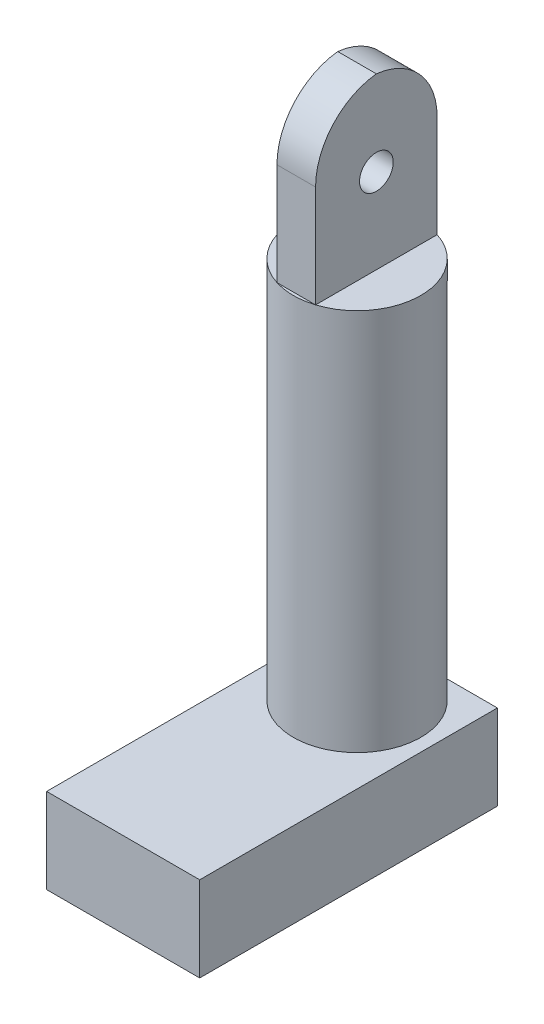
SolidWorks part; units mm, degrees
ref_plane "Front Plane" through (0, 0, 0) normal (0, 0, 1) x (1, 0, 0)
ref_plane "Top Plane" through (0, 0, 0) normal (0, 1, 0) x (1, 0, 0)
ref_plane "Right Plane" through (0, 0, 0) normal (1, 0, 0) x (0, 0, -1)
sketch "Sketch1" plane through (0, 0, 0) normal (0, 1, 0) x (1, 0, 0)
  line L2 (-90, -175) -> (90, -175)
  line L3 (-90, -175) -> (-90, 175)
  line L4 (-90, 175) -> (90, 175)
  line L5 (90, -175) -> (90, 175)
  line L6 (-90, -175) -> (90, 175) construction
  line L7 (-90, 175) -> (90, -175) construction
  point P0 (0, 0)
  dimension "D1" = 180
  dimension "D3" = 350
extrude "Boss-Extrude1" add sketch "Sketch1" along normal blind 100
sketch "Sketch2" plane through (0, 100, 0) normal (0, 1, 0) x (1, 0, 0)
  line L0 (0, 175) -> (0, -175) construction
  line L1 (90, 175) -> (-90, 175) construction
  line L2 (-90, -175) -> (90, -175) construction
  circle A0 centre (0, 100) radius 75
  dimension "D1" = 150
  dimension "D3" = 75
extrude "Boss-Extrude2" add sketch "Sketch2" along normal blind 450
sketch "Sketch3" plane through (0, 550, 0) normal (0, 1, 0) x (1, 0, 0)
  line L1 (-22.7097, 28.5208) -> (22.7097, 28.5208)
  line L2 (-22.7097, 28.5208) -> (-22.7097, 171.4792)
  line L3 (-22.7097, 171.4792) -> (22.7097, 171.4792)
  line L4 (22.7097, 28.5208) -> (22.7097, 171.4792)
  line L5 (-22.7097, 28.5208) -> (22.7097, 171.4792) construction
  line L6 (-22.7097, 171.4792) -> (22.7097, 28.5208) construction
  circle A0 centre (0, 100) radius 75 construction
  point P0 (0, 100)
extrude "Boss-Extrude3" add sketch "Sketch3" along normal blind 200
fillet "Fillet1" radius 80 2 edges at (0, 750, -171.4792) (0, 750, -28.5208)
sketch "Sketch4" plane through (-22.7097, 0, 0) normal (1, 0, 0) x (0, 0, -1)
  line L0 (100, 749.5449) -> (100, 550) construction
  line L2 (171.4792, 550) -> (28.5208, 550) construction
  circle A1 centre (100, 649.7725) radius 19.8124
  point P2 (0, 0)
  point P3 (100, 749.5449)
  point P5 (100, 550)
  point P8 (0, 0)
extrude "Cut-Extrude1" cut sketch "Sketch4" against normal through all both and the other way through all
